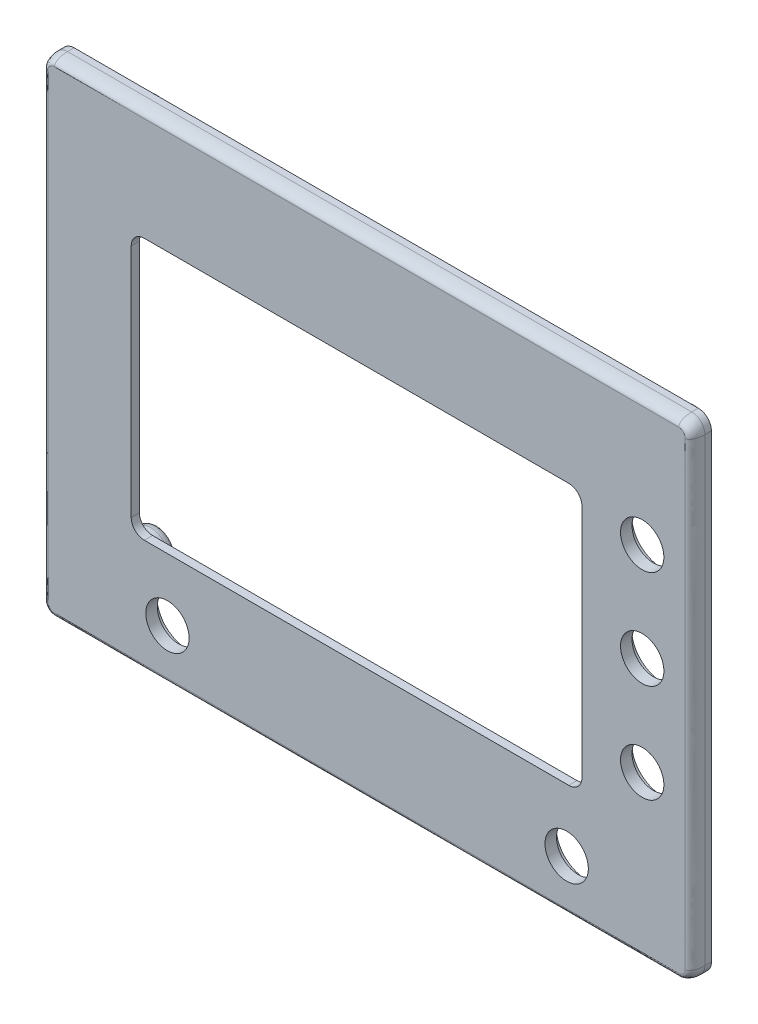
SolidWorks part; units mm, degrees
material "ABS"
ref_plane "Płaszczyzna przednia" through (0, 0, 0) normal (0, 0, 1) x (1, 0, 0)
ref_plane "Płaszczyzna górna" through (0, 0, 0) normal (0, 1, 0) x (1, 0, 0)
ref_plane "Płaszczyzna prawa" through (0, 0, 0) normal (1, 0, 0) x (0, 0, -1)
sketch "Szkic1" plane through (0, 0, 0) normal (0, 0, 1) x (1, 0, 0)
  line L4 (47.5, 37.1) -> (-47.5, 37.1)
  line L5 (49.6, -35) -> (49.6, 35)
  line L6 (-47.5, -37.1) -> (47.5, -37.1)
  line L7 (-49.6, 35) -> (-49.6, -35)
  line L8 (47.5, 37) -> (-47.5, 37)
  line L9 (-49.5, 35) -> (-49.5, -35)
  line L10 (-47.5, -37) -> (47.5, -37)
  line L11 (49.5, -35) -> (49.5, 35)
  arc A4 (49.6, 35) -> (47.5, 37.1) centre (47.5, 35) ccw
  arc A5 (47.5, -37.1) -> (49.6, -35) centre (47.5, -35) ccw
  arc A6 (-49.6, -35) -> (-47.5, -37.1) centre (-47.5, -35) ccw
  arc A7 (-47.5, 37.1) -> (-49.6, 35) centre (-47.5, 35) ccw
  arc A8 (-47.5, 37) -> (-49.5, 35) centre (-47.5, 35) ccw
  arc A9 (-49.5, -35) -> (-47.5, -37) centre (-47.5, -35) ccw
  arc A10 (47.5, -37) -> (49.5, -35) centre (47.5, -35) ccw
  arc A11 (49.5, 35) -> (47.5, 37) centre (47.5, 35) ccw
extrude "Dodanie-wyciągnięcie1" add sketch "Szkic1" along normal blind 3 contours L11 A11 L8 A8 L9 A9 L10 A10
hole_wizard "Otwór Ø3.0 (3)1" positions "Szkic3" profile "Szkic4" hole size "Ø3.0" standard "BSI"
sketch "Szkic3" plane through (0, 0, 3) normal (0, 0, 1) x (1, 0, 0)
  point P0 (-40.925, 28.425)
  point P3 (40.925, 28.425)
  point P6 (40.925, -28.425)
  point P9 (-40.925, -28.425)
sketch "Szkic4" plane through (-40.925, 28.425, 3) normal (1, 0, 0) x (0, -1, 0)
  line L0 (0, 0) -> (0, 19.9513)
  line L1 (0, 19.9513) -> (1.5, 19.05)
  line L2 (1.5, 19.05) -> (1.5, 0)
  line L5 (1.5, 0) -> (0, 0)
  line L10 (0, 19.9513) -> (-1.5, 19.05) construction
  line L11 (0, -6.35) -> (0, 107.95) construction
  dimension "Średnica otworu" = 3
  dimension "Głębokość otworu" = 19.05
  dimension "Kąt wiertła" = 118
hole_wizard "Otwór Ø6.0 (6)1" positions "Szkic6" profile "Szkic7" hole size "Ø6.0" standard "BSI"
sketch "Szkic6" plane through (0, 0, 3) normal (0, 0, 1) x (1, 0, 0)
  point P0 (41.96, 17.73)
  point P3 (41.96, 2.73)
  point P6 (41.96, -12.27)
  point P9 (30.46, -29.07)
  point P12 (-30.3, -29.07)
sketch "Szkic7" plane through (41.96, 17.73, 3) normal (1, 0, 0) x (0, -1, 0)
  line L0 (0, 0) -> (0, 20.8526)
  line L1 (0, 20.8526) -> (3, 19.05)
  line L2 (3, 19.05) -> (3, 0)
  line L5 (3, 0) -> (0, 0)
  line L10 (0, 20.8526) -> (-3, 19.05) construction
  line L11 (0, -6.35) -> (0, 107.95) construction
  dimension "Średnica otworu" = 6
  dimension "Głębokość otworu" = 19.05
  dimension "Kąt wiertła" = 118
sketch "Szkic8" plane through (0, 0, 3) normal (0, 0, 1) x (1, 0, 0)
  line L0 (-35.8135, 20.23) -> (-35.8135, -19.57)
  line L1 (-35.8135, -19.57) -> (32.7865, -19.57)
  line L2 (32.7865, -19.57) -> (32.7865, 20.23)
  line L3 (32.7865, 20.23) -> (-35.8135, 20.23)
  line L4 (-35.8135, 20.23) -> (32.7865, 20.23)
  line L5 (32.7865, 20.23) -> (32.7865, 26.93)
  line L6 (32.7865, 26.93) -> (-35.8135, 26.93)
  line L7 (-35.8135, 26.93) -> (-35.8135, 20.23)
  line L8 (32.7865, -19.57) -> (-35.8135, -19.57)
  line L9 (-35.8135, -19.57) -> (-35.8135, -21.67)
  line L10 (-35.8135, -21.67) -> (32.7865, -21.67)
  line L11 (32.7865, -21.67) -> (32.7865, -19.57)
  line L12 (-35.8135, -15.1511) -> (-35.8135, 24.8489)
  line L13 (-35.8135, 24.8489) -> (-42.6039, 13.8489)
  line L14 (-42.6039, 13.8489) -> (-42.6039, -4.1511)
  line L15 (-42.6039, -4.1511) -> (-35.8135, -15.1511)
  line L16 (49.5, -35) -> (49.5, 35)
  line L17 (47.5, 37) -> (-47.5, 37)
  line L18 (-49.5, 35) -> (-49.5, -35)
  line L19 (-47.5, -37) -> (47.5, -37)
  circle A0 centre (40.925, -28.425) radius 1.6
  circle A1 centre (-40.925, -28.425) radius 1.6
  circle A2 centre (-40.925, 28.425) radius 1.6
  circle A3 centre (40.925, 28.425) radius 1.6
  arc A4 (49.5, 35) -> (47.5, 37) centre (47.5, 35) ccw
  arc A5 (-47.5, 37) -> (-49.5, 35) centre (-47.5, 35) ccw
  arc A6 (-49.5, -35) -> (-47.5, -37) centre (-47.5, -35) ccw
  arc A7 (47.5, -37) -> (49.5, -35) centre (47.5, -35) ccw
  circle A8 centre (41.96, 17.73) radius 3
  circle A9 centre (41.96, 2.73) radius 3
  circle A10 centre (41.96, -12.27) radius 3
  circle A11 centre (30.46, -29.07) radius 3
  circle A12 centre (-30.3, -29.07) radius 3
extrude "Wytnij-wyciągnięcie1" cut sketch "Szkic8" against normal through all contours L2 L3 L0 L1
sketch "Szkic9" plane through (0, 0, 0) normal (0, 0, -1) x (-1, 0, 0)
  line L8 (38.8135, -22.57) -> (38.8135, 23.23)
  line L9 (-35.7865, -22.57) -> (38.8135, -22.57)
  line L10 (-35.7865, 23.23) -> (-35.7865, -22.57)
  line L11 (38.8135, 23.23) -> (-35.7865, 23.23)
  line L12 (38.8135, -22.57) -> (38.8135, 23.23)
  line L13 (-35.7865, -22.57) -> (38.8135, -22.57)
  line L14 (-35.7865, 23.23) -> (-35.7865, -22.57)
  line L15 (38.8135, 23.23) -> (-35.7865, 23.23)
  dimension "D1" = 3
extrude "Wytnij-wyciągnięcie2" cut sketch "Szkic9" against normal blind 1.75
fillet "Zaokrąglenie1" radius 2 4 edges at (32.7865, -19.57, 2.375) (-35.8135, -19.57, 2.375) (-35.8135, 20.23, 2.375) (32.7865, 20.23, 2.375)
sketch "Szkic10" plane through (0, 0, 1.75) normal (0, 0, -1) x (-1, 0, 0)
  line L0 (-34.7865, 18.23) -> (-34.7865, -17.57)
  line L1 (-30.7865, -21.57) -> (33.8135, -21.57)
  line L2 (37.8135, -17.57) -> (37.8135, 18.23)
  line L3 (33.8135, 22.23) -> (-30.7865, 22.23)
  line L8 (-33.7865, 18.23) -> (-33.7865, -17.57)
  line L9 (-30.7865, -20.57) -> (33.8135, -20.57)
  line L10 (36.8135, -17.57) -> (36.8135, 18.23)
  line L11 (33.8135, 21.23) -> (-30.7865, 21.23)
  line L12 (-33.7865, 18.23) -> (-33.7865, -17.57)
  line L13 (-30.7865, -20.57) -> (33.8135, -20.57)
  line L14 (36.8135, -17.57) -> (36.8135, 18.23)
  line L15 (33.8135, 21.23) -> (-30.7865, 21.23)
  arc A0 (-34.7865, -17.57) -> (-30.7865, -21.57) centre (-30.7865, -17.57) ccw
  arc A1 (33.8135, -21.57) -> (37.8135, -17.57) centre (33.8135, -17.57) ccw
  arc A2 (37.8135, 18.23) -> (33.8135, 22.23) centre (33.8135, 18.23) ccw
  arc A3 (-30.7865, 22.23) -> (-34.7865, 18.23) centre (-30.7865, 18.23) ccw
  arc A8 (-33.7865, -17.57) -> (-30.7865, -20.57) centre (-30.7865, -17.57) ccw
  arc A9 (33.8135, -20.57) -> (36.8135, -17.57) centre (33.8135, -17.57) ccw
  arc A10 (36.8135, 18.23) -> (33.8135, 21.23) centre (33.8135, 18.23) ccw
  arc A11 (-30.7865, 21.23) -> (-33.7865, 18.23) centre (-30.7865, 18.23) ccw
  arc A12 (-33.7865, -17.57) -> (-30.7865, -20.57) centre (-30.7865, -17.57) ccw
  arc A13 (33.8135, -20.57) -> (36.8135, -17.57) centre (33.8135, -17.57) ccw
  arc A14 (36.8135, 18.23) -> (33.8135, 21.23) centre (33.8135, 18.23) ccw
  arc A15 (-30.7865, 21.23) -> (-33.7865, 18.23) centre (-30.7865, 18.23) ccw
  dimension "D1" = 1
  dimension "D2" = 1
extrude "Wytnij-wyciągnięcie3" cut sketch "Szkic10" against normal blind 0.5
sketch "Szkic12" plane through (0, 0, 0) normal (0, 0, -1) x (-1, 0, 0)
  circle A0 centre (-40.925, -28.425) radius 1.5 construction
  circle A1 centre (40.925, -28.425) radius 1.5 construction
  circle A2 centre (40.925, 28.425) radius 1.5 construction
  circle A3 centre (-40.925, 28.425) radius 1.5 construction
  circle A4 centre (-40.925, -28.425) radius 1.5
  circle A5 centre (40.925, -28.425) radius 1.5
  circle A6 centre (40.925, 28.425) radius 1.5
  circle A7 centre (-40.925, 28.425) radius 1.5
  circle A8 centre (-40.925, 28.425) radius 3
  circle A9 centre (40.925, 28.425) radius 3
  circle A10 centre (40.925, -28.425) radius 3
  circle A11 centre (-40.925, -28.425) radius 3
  dimension "D1" = 1.5
extrude "Dodanie-wyciągnięcie2" add sketch "Szkic12" along normal blind 6
fillet "Zaokrąglenie2" radius 2 4 edges at (43.925, -28.425, 0) (-37.925, -28.425, 0) (-37.925, 28.425, 0) (43.925, 28.425, 0)
sketch "Szkic13" plane through (0, 0, 0) normal (0, 0, -1) x (-1, 0, 0)
  circle A0 centre (30.3, -29.07) radius 3 construction
  circle A1 centre (-30.46, -29.07) radius 3 construction
  circle A2 centre (-41.96, 17.73) radius 3 construction
  circle A3 centre (-41.96, 2.73) radius 3 construction
  circle A4 centre (-41.96, -12.27) radius 3 construction
  circle A10 centre (30.3, -29.07) radius 3 construction
  circle A11 centre (-30.46, -29.07) radius 3 construction
  circle A12 centre (-41.96, -12.27) radius 3 construction
  circle A13 centre (-41.96, 2.73) radius 3 construction
  circle A14 centre (-41.96, 17.73) radius 3 construction
  circle A15 centre (-41.96, -12.27) radius 3.3
  circle A16 centre (-41.96, 2.73) radius 3.3
  circle A17 centre (-41.96, 17.73) radius 3.3
  circle A18 centre (-30.46, -29.07) radius 3.3
  circle A19 centre (30.3, -29.07) radius 3.3
  dimension "D1" = 0.3
extrude "Wytnij-wyciągnięcie4" cut sketch "Szkic13" against normal through all
sketch "Szkic14" plane through (0, 0, 0) normal (0, 0, -1) x (-1, 0, 0)
  circle A0 centre (30.3, -29.07) radius 3.3 construction
  circle A1 centre (-30.46, -29.07) radius 3.3 construction
  circle A2 centre (-41.96, 17.73) radius 3.3 construction
  circle A3 centre (-41.96, 2.73) radius 3.3 construction
  circle A4 centre (-41.96, -12.27) radius 3.3 construction
  circle A5 centre (30.3, -29.07) radius 3.3 construction
  circle A6 centre (-30.46, -29.07) radius 3.3 construction
  circle A7 centre (-41.96, 17.73) radius 3.3 construction
  circle A8 centre (-41.96, 2.73) radius 3.3 construction
  circle A9 centre (-41.96, -12.27) radius 3.3 construction
  circle A10 centre (-41.96, 17.73) radius 4.6
  circle A11 centre (-41.96, 2.73) radius 4.6
  circle A12 centre (-41.96, -12.27) radius 4.6
  circle A13 centre (-30.46, -29.07) radius 4.6
  circle A14 centre (30.3, -29.07) radius 4.6
  dimension "D1" = 1.3
extrude "Wytnij-wyciągnięcie5" cut sketch "Szkic14" against normal blind 1.25
fillet "Zaokrąglenie3" radius 0.5 4 edges at (37.925, -28.425, -6) (-43.925, -28.425, -6) (-43.925, 28.425, -6) (37.925, 28.425, -6)
sketch "Szkic15" plane through (0, 0, 3) normal (0, 0, 1) x (1, 0, 0)
  circle A0 centre (40.925, 28.425) radius 1.5 construction
  circle A1 centre (-40.925, 28.425) radius 1.5 construction
  circle A2 centre (-40.925, -28.425) radius 1.5 construction
  circle A3 centre (40.925, -28.425) radius 1.5 construction
  circle A4 centre (40.925, 28.425) radius 1.5
  circle A5 centre (-40.925, 28.425) radius 1.5
  circle A6 centre (-40.925, -28.425) radius 1.5
  circle A7 centre (40.925, -28.425) radius 1.5
extrude "Dodanie-wyciągnięcie3" add sketch "Szkic15" against normal blind 1
fillet "Zaokrąglenie4" radius 1 8 edges at (0, 37, 3) (-48.9142, 36.4142, 3) (48.9142, 36.4142, 3) (-49.5, 0, 3) (49.5, 0, 3) (-48.9142, -36.4142, 3) (48.9142, -36.4142, 3) (0, -37, 3)
